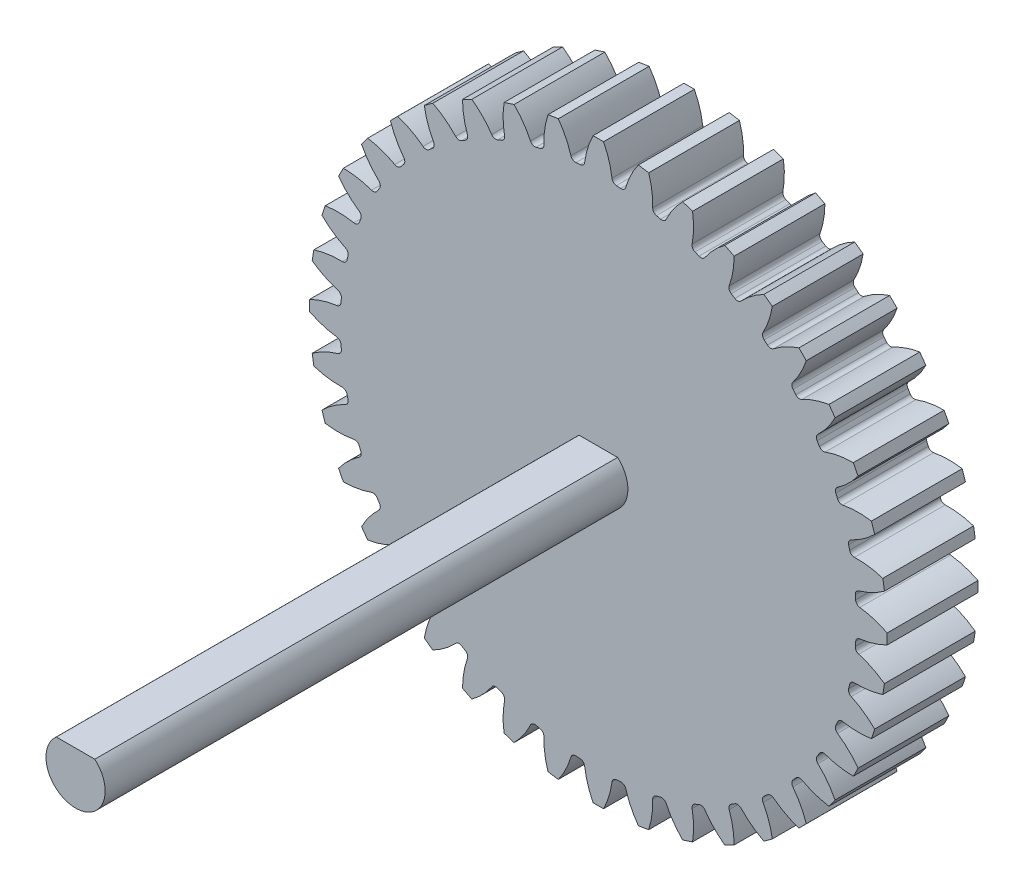
SolidWorks part; units mm, degrees
material "ABS"
ref_plane "Plane1" through (0, 0, 0) normal (0, 0, 1) x (1, 0, 0)
ref_plane "Plane2" through (0, 0, 0) normal (0, 1, 0) x (1, 0, 0)
ref_plane "Plane3" through (0, 0, 0) normal (1, 0, 0) x (0, 0, -1)
sketch "Esquisse1" plane through (0, 0, 0) normal (0, 0, 1) x (1, 0, 0)
  circle A0 centre (0, 0) radius 1.15
  dimension "D1" = 2.3
extrude "Base-Extrusion" add sketch "Esquisse1" along normal blind 2.5
sketch "Parametres" plane through (0, 0, 2.5) normal (0, 0, 1) x (1, 0, 0)
  line L0 (-33.4711, 41.7411) -> (6.5289, 41.7411)
  line L1 (-33.4711, 34.0759) -> (-32.9711, 34.0759)
  line L2 (-33.4711, 23.0892) -> (-13.4711, 23.0892)
  line L3 (-33.4711, -2.6579) -> (-33.1221, -2.6579)
  line L4 (-38.9094, -12.5583) -> (-35.7678, -12.5583)
  line L5 (-48.8826, -19.2556) -> (-38.8826, -19.2556)
  line L6 (-48.8826, -29.9283) -> (-38.3826, -29.9283)
  line L7 (-48.8826, -38.2322) -> (-39.5076, -38.2322)
  line L8 (-48.8826, -45.1309) -> (-39.4856, -45.1309)
  line L9 (-48.8826, -60.7647) -> (-48.0972, -60.7647)
  line L10 (-48.8826, -76.1039) -> (-47.8644, -76.1039)
  line L11 (-48.8826, -88.0795) -> (-48.4201, -88.0795)
  line L12 (-48.8826, -98.8973) -> (-48.5022, -98.8973)
  line L13 (16.9123, -61.9871) -> (21.4123, -61.9871)
  line L14 (18.5152, -81.0212) -> (24.7231, -81.0212)
  line L15 (18.5152, -96.0481) -> (20.5906, -96.0481)
  line L16 (-33.4711, 13.8609) -> (-26.8711, 13.8609)
sketch "Esquisse3" plane through (0, 0, 0) normal (0, 0, 1) x (1, 0, 0)
  line L0 (0, 0) -> (0, 29.3764) construction
  line L1 (-0.7356, 9.3461) -> (0, 0)
  line L2 (0, 0) -> (0.7356, 9.3461)
  line L3 (0, 0) -> (0.5088, 9.3831) construction
  line L4 (0, 0) -> (0.1902, 10.4983) construction
  line L5 (0, 0) -> (0.3926, 9.9923) construction
  arc A0 (0.1902, 10.4983) -> (0.5107, 9.3611) centre (-2.5179, 9.1213) cw
  arc A1 (-0.1902, 10.4983) -> (-0.5107, 9.3611) centre (2.5179, 9.1213) ccw
  arc A2 (0.7356, 9.3461) -> (0.5107, 9.3611) centre (0, 0) ccw
  arc A3 (-0.7356, 9.3461) -> (-0.5107, 9.3611) centre (0, 0) cw
  arc A4 (0.1902, 10.4983) -> (-0.1902, 10.4983) centre (0, 0) ccw
  dimension "D4" = 9
  dimension "D5" = 9.3969
  dimension "D6" = 10
  dimension "D1" = 10.5
  dimension "D2" = 3.104
  dimension "D3" = 2.25
  dimension "D7" = 1.038
  dimension "D8" = 9.375
extrude "Boss.-Extru.1" add sketch "Esquisse3" along normal blind 3.3
fillet "Congé1" radius 0.175 2 edges at (0.5107, 9.3611, 1.65) (-0.5107, 9.3611, 1.65)
ref_axis "Axe1" through (0, 0, 53.3) along (0, 0, -1)
pattern_circular "Répétition circulaire4" count 40 every 9 about axis through (0, 0, 53.3) along (0, 0, -1) of "Boss.-Extru.1", "Congé1"
sketch "Esquisse4" plane through (0, 0, 3.3) normal (0, 0, 1) x (1, 0, 0)
  line L0 (-0.7, 0.8159) -> (0.7, 0.8159)
  arc A0 (-0.7, 0.8159) -> (0.7, 0.8159) centre (0, 0) ccw
  dimension "D1" = 2.15
  dimension "D2" = 1.4
extrude "Boss.-Extru.2" add sketch "Esquisse4" along normal blind 19
sketch "Esquisse5" plane through (0, 0, 0) normal (0, 0, -1) x (-1, 0, 0)
  circle A0 centre (0, 0) radius 1
  dimension "D1" = 2
extrude "Enlèv. mat.-Extru.1" cut sketch "Esquisse5" against normal blind 3
sketch "Esquisse6" plane through (0, 0, 0) normal (0, 0, -1) x (-1, 0, 0)
  circle A1 centre (0, 0) radius 1
  circle A2 centre (0, 0) radius 2
  circle A3 centre (0, 0) radius 2
  dimension "D1" = 1
extrude "Boss.-Extru.3" add sketch "Esquisse6" along normal blind 3
equation "\"PI@Parametres\" = 3.141592654"
equation "\"Alpha_rad@Parametres\" = \"Alpha@Parametres\"*\"PI@Parametres\"/180"
equation "\"R@Parametres\" = \"Z@Parametres\"*\"m@Parametres\"/2"
equation "\"RT@Parametres\" = \"R@Parametres\"+\"m@Parametres\""
equation "\"RP@Parametres\" = \"R@Parametres\"-1.25*\"m@Parametres\""
equation "\"Rb@Parametres\" = \"R@Parametres\"*cos(\"Alpha_rad@Parametres\")"
equation "\"E@Parametres\" = \"PI@Parametres\"*\"R@Parametres\"/\"Z@Parametres\""
equation "\"Eb@Parametres\" = \"Rb@Parametres\"*((\"PI@Parametres\"*\"m@Parametres\"/(2*\"R@Parametres\"))+2*(tan(\"Alpha_rad@Parametres\")-\"Alpha_rad@Parametres\"))"
equation "\"As@Parametres\" = atn(sqr(\"RT@Parametres\"*\"RT@Parametres\"-\"Rb@Parametres\"*\"Rb@Parametres\")/\"Rb@Parametres\")"
equation "\"Et@Parametres\" = \"RT@Parametres\"*((\"E@Parametres\"/\"R@Parametres\")+2*(tan(\"Alpha_rad@Parametres\")-\"Alpha_rad@Parametres\"-tan(\"As@Parametres\")+\"As@Parametres\"))"
equation "\"Ap@Parametres\" = (\"E@Parametres\"/\"R@Parametres\")*180/\"PI@Parametres\""
equation "\"Ab@Parametres\" = (\"Eb@Parametres\"/\"Rb@Parametres\")*180/\"PI@Parametres\""
equation "\"At@Parametres\" = (\"Et@Parametres\"/\"RT@Parametres\")*180/\"PI@Parametres\""
equation "\"D7@Esquisse3\" = \"At@Parametres\"/2"
equation "\"D3@Esquisse3\"=\"Ap@Parametres\"/2"
equation "\"D2@Esquisse3\"=\"Ab@Parametres\"/2"
equation "\"D5@Esquisse3\"=\"Rb@Parametres\""
equation "\"D6@Esquisse3\"=\"R@Parametres\""
equation "\"D1@Esquisse3\"=\"RT@Parametres\""
equation "\"D4@Esquisse3\" = \"Ap@Parametres\"*2"
equation "\"D1@Boss.-Extru.1\" = \"k@Parametres\"*\"m@Parametres\""
equation "\"D1@Congé1\" = 0.35*\"m@Parametres\""
equation "\"D2@Répétition circulaire4\" = \"Ap@Parametres\"*2"
equation "\"D1@Répétition circulaire4\" = \"Z@Parametres\""
equation "\"D8@Esquisse3\" = \"RP@Parametres\""
